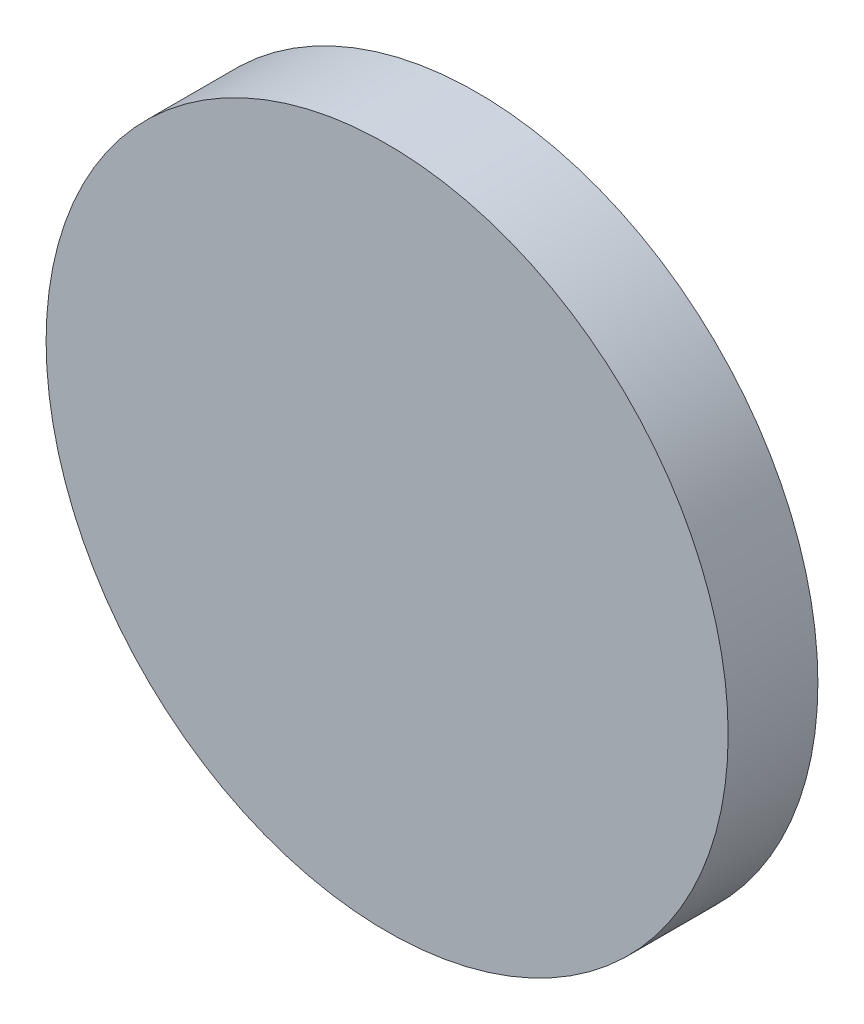
SolidWorks part; units mm, degrees
ref_plane "Front Plane" through (0, 0, 0) normal (0, 0, 1) x (1, 0, 0)
ref_plane "Top Plane" through (0, 0, 0) normal (0, 1, 0) x (1, 0, 0)
ref_plane "Right Plane" through (0, 0, 0) normal (1, 0, 0) x (0, 0, -1)
sketch "Sketch1" plane through (0, 0, 0) normal (0, 0, 1) x (1, 0, 0)
  circle A0 centre (-81.1281, 39.6078) radius 9.5
  dimension "D1" = 19
extrude "Boss-Extrude1" add sketch "Sketch1" along normal blind 2.5
ref_axis "Axis1" through (-81.1281, 39.6078, 2.5) along (0, 0, -1)
